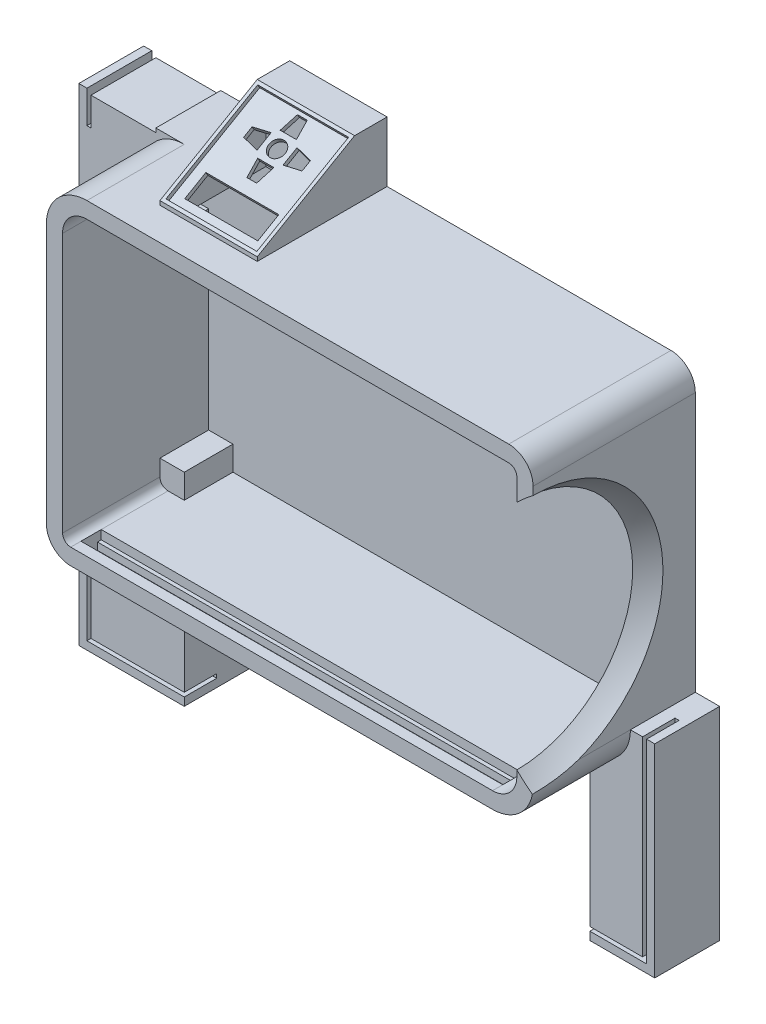
SolidWorks part; units mm, degrees
ref_plane "Front Plane" through (0, 0, 0) normal (0, 0, 1) x (1, 0, 0)
ref_plane "Top Plane" through (0, 0, 0) normal (0, 1, 0) x (1, 0, 0)
ref_plane "Right Plane" through (0, 0, 0) normal (1, 0, 0) x (0, 0, -1)
sketch "Sketch1" plane through (0, 0, 0) normal (0, 0, 1) x (1, 0, 0)
  line L1 (-190.5, -127) -> (190.5, -127)
  line L2 (-190.5, -127) -> (-190.5, 127)
  line L3 (-190.5, 127) -> (190.5, 127)
  line L4 (190.5, -127) -> (190.5, 127)
  line L5 (-190.5, -127) -> (190.5, 127) construction
  line L6 (-190.5, 127) -> (190.5, -127) construction
  point P0 (0, 0)
  dimension "D1" = 381
  dimension "D2" = 254
extrude "Boss-Extrude1" add sketch "Sketch1" against normal blind 127
fillet "Fillet5" radius 19.05 2 edges at (-190.5, -127, -63.5) (190.5, 127, -63.5)
fillet "Fillet4" radius 31.75 2 edges at (190.5, -127, -63.5) (-190.5, 127, -63.5)
sketch "Sketch3" plane through (0, 0, 0) normal (0, 0, -1) x (-1, 0, 0)
  line L16 (-158.75, -114.3) -> (171.45, -114.3)
  line L17 (-177.8, 107.95) -> (-177.8, -95.25)
  line L18 (158.75, 114.3) -> (-171.45, 114.3)
  line L19 (177.8, -107.95) -> (177.8, 95.25)
  line L20 (-158.75, -114.3) -> (171.45, -114.3)
  line L21 (-177.8, 107.95) -> (-177.8, -95.25)
  line L22 (158.75, 114.3) -> (-171.45, 114.3)
  line L23 (177.8, -107.95) -> (177.8, 95.25)
  arc A13 (-177.8, -95.25) -> (-158.75, -114.3) centre (-158.75, -95.25) ccw
  arc A14 (-171.45, 114.3) -> (-177.8, 107.95) centre (-171.45, 107.95) ccw
  arc A15 (177.8, 95.25) -> (158.75, 114.3) centre (158.75, 95.25) ccw
  arc A16 (171.45, -114.3) -> (177.8, -107.95) centre (171.45, -107.95) ccw
  arc A17 (-177.8, -95.25) -> (-158.75, -114.3) centre (-158.75, -95.25) ccw
  arc A18 (-171.45, 114.3) -> (-177.8, 107.95) centre (-171.45, 107.95) ccw
  arc A19 (177.8, 95.25) -> (158.75, 114.3) centre (158.75, 95.25) ccw
  arc A20 (171.45, -114.3) -> (177.8, -107.95) centre (171.45, -107.95) ccw
  dimension "D1" = 12.7
extrude "Cut-Extrude1" cut sketch "Sketch3" along normal offset from surface (114.3 mm away) 12.7 up to face at (0, 0, -127)
sketch "Sketch5" plane through (0, -127, 0) normal (0, -1, 0) x (1, 0, 0)
  line L0 (158.75, -127) -> (158.75, 0) construction
  line L1 (158.75, -10.455) -> (-171.45, -10.455)
  line L2 (158.75, -10.455) -> (158.75, -20.955)
  line L3 (158.75, -20.955) -> (-171.45, -20.955)
  line L4 (-171.45, -10.455) -> (-171.45, -20.955)
  line L5 (-171.45, 0) -> (-171.45, -127) construction
  line L7 (-171.45, 0) -> (158.75, 0) construction
  dimension "D1" = 10.5
  dimension "D2" = 20.955
extrude "Cut-Extrude2" cut sketch "Sketch5" against normal up to next
ref_plane "Plane1" through (0, 0, 0) normal (0, 1, 0) x (1, 0, 0)
sketch "Sketch6" plane through (0, 0, 0) normal (0, 1, 0) x (1, 0, 0)
  line L0 (139.7, 0) -> (266.7, 0)
  line L1 (171.45, 0) -> (-158.75, 0) construction
  line L2 (266.7, 0) -> (266.7, 127)
  line L3 (171.45, 127) -> (-158.75, 127) construction
  line L4 (190.5, 127) -> (190.5, 0) construction
  arc A0 (139.7, 0) -> (266.7, 127) centre (266.7, 0) cw
  dimension "D1" = 76.2
revolve "Cut-Revolve1" cut sketch "Sketch6" angle 360 about L2
sketch "Sketch7" plane through (0, 0, -127) normal (0, 0, -1) x (-1, 0, 0)
  line L0 (190.5, 95.25) -> (190.5, -107.95) construction
  line L1 (158.75, 127) -> (241.3, 127)
  line L2 (158.75, 127) -> (158.75, 50.8)
  line L3 (158.75, 50.8) -> (241.3, 50.8)
  line L4 (241.3, 127) -> (241.3, 50.8)
  line L5 (171.45, -127) -> (-158.75, -127) construction
  line L6 (234.95, 127) -> (231.775, 127)
  line L7 (234.95, 127) -> (234.95, 101.6)
  line L8 (234.95, 101.6) -> (231.775, 101.6)
  line L9 (231.775, 127) -> (231.775, 101.6)
  line L10 (-158.75, -95.25) -> (-209.55, -95.25)
  line L11 (-158.75, -95.25) -> (-158.75, -254)
  line L12 (-158.75, -254) -> (-209.55, -254)
  line L13 (-209.55, -95.25) -> (-209.55, -254)
  line L14 (0, 127) -> (0, -127) construction
  line L15 (-171.45, 127) -> (158.75, 127) construction
  line L16 (158.75, -254) -> (241.3, -254)
  line L17 (241.3, -95.25) -> (241.3, -254)
  line L18 (158.75, -95.25) -> (241.3, -95.25)
  line L19 (158.75, -95.25) -> (158.75, -254)
  line L21 (231.775, 127) -> (180.975, 127)
  line L22 (231.775, 127) -> (231.775, 123.825)
  line L23 (231.775, 123.825) -> (180.975, 123.825)
  line L24 (180.975, 127) -> (180.975, 123.825)
  line M11 (190.5, -107.95) -> (190.5, 95.25)
  arc M12 (190.5, 95.25) -> (158.75, 127) centre (158.75, 95.25) ccw
  dimension "D1" = 50.8
  dimension "D2" = 76.2
  dimension "D3" = 3.175
  dimension "D4" = 6.35
  dimension "D5" = 25.4
  dimension "D6" = 50.8
  dimension "D7" = 127
  dimension "D8" = 50.8
extrude "Boss-Extrude2" add sketch "Sketch7" against normal blind 50.8 contours L9 L1 L3 L4 L7 L8 M12 M11 | L16 L17 L18 L19 | L11 L10 L13 L12 region at (-214.1054, 88.5803, -127)
sketch "Sketch8" plane through (0, 0, -76.2) normal (0, 0, 1) x (1, 0, 0)
  line L0 (-234.95, -95.25) -> (-234.95, -247.65)
  line L1 (-190.5, -95.25) -> (-241.3, -95.25) construction
  line L2 (-234.95, -247.65) -> (-158.75, -247.65)
  line L3 (-158.75, -127) -> (-158.75, -254) construction
  line L4 (-158.75, -247.65) -> (-158.75, -244.475)
  line L5 (-158.75, -244.475) -> (-231.775, -244.475)
  line L6 (-231.775, -244.475) -> (-231.775, -95.25)
  line L7 (-231.775, -95.25) -> (-234.95, -95.25)
  line L8 (-234.95, 101.6) -> (-231.775, 101.6) construction
  line L9 (-234.95, 127) -> (-234.95, 101.6) construction
  line L10 (-158.75, -254) -> (-241.3, -254) construction
  line L11 (158.75, -247.65) -> (203.2, -247.65)
  line L12 (158.75, -127) -> (158.75, -254) construction
  line L13 (203.2, -247.65) -> (203.2, -95.25)
  line L14 (190.5, -95.25) -> (209.55, -95.25) construction
  line L15 (203.2, -95.25) -> (200.025, -95.25)
  line L16 (200.025, -95.25) -> (200.025, -244.475)
  line L17 (200.025, -244.475) -> (158.75, -244.475)
  line L18 (158.75, -244.475) -> (158.75, -247.65)
  line L19 (209.55, -95.25) -> (209.55, -254) construction
  dimension "D1" = 6.35
  dimension "D2" = 6.35
extrude "Cut-Extrude3" cut sketch "Sketch8" against normal blind 25.4
ref_plane "Plane2" through (-127, 0, 0) normal (1, 0, 0) x (0, 0, -1)
sketch "Sketch9" plane through (-127, 0, 0) normal (1, 0, 0) x (0, 0, -1)
  line L0 (25.4, 127) -> (25.4, 130.175)
  line L1 (0, 127) -> (127, 127) construction
  line L2 (25.4, 130.175) -> (101.6, 174.1691)
  line L4 (25.4, 127) -> (127, 127)
  line L5 (0, 127) -> (0, 107.95) construction
  line L6 (101.6, 174.1691) -> (127, 174.1691)
  line L7 (127, 174.1691) -> (127, 127)
  line L8 (127, 107.95) -> (127, 127) construction
  dimension "D1" = 25.4
  dimension "D3" = 25.4
  dimension "D4" = 3.175
  dimension "D5" = 60
extrude "Boss-Extrude3" add sketch "Sketch9" along normal blind 76.2
sketch "Sketch10" plane through (0, 86.6327, 50.0174) normal (0, 0.866, 0.5) x (1, 0, 0)
  line L8 (-124.46, 172.5327) -> (-124.46, 89.6245)
  line L9 (-124.46, 89.6245) -> (-53.34, 89.6245)
  line L10 (-53.34, 89.6245) -> (-53.34, 172.5327)
  line L11 (-53.34, 172.5327) -> (-124.46, 172.5327)
  line L12 (-124.46, 172.5327) -> (-124.46, 89.6245)
  line L13 (-124.46, 89.6245) -> (-53.34, 89.6245)
  line L14 (-53.34, 89.6245) -> (-53.34, 172.5327)
  line L15 (-53.34, 172.5327) -> (-124.46, 172.5327)
  dimension "D1" = 2.54
extrude "Cut-Extrude4" cut sketch "Sketch10" against normal blind 12.7
sketch "Sketch11" plane through (0, 114.3, 0) normal (0, -1, 0) x (1, 0, 0)
  line L0 (-124.46, -33.9497) -> (-53.34, -33.9497) construction
  line L1 (-124.46, -33.9497) -> (-53.34, -33.9497)
  line L2 (-124.46, -33.9497) -> (-124.46, -105.7503)
  line L3 (-124.46, -105.7503) -> (-53.34, -105.7503)
  line L4 (-53.34, -33.9497) -> (-53.34, -105.7503)
  line L5 (-124.46, -105.7503) -> (-124.46, -33.9497) construction
  line L6 (-53.34, -105.7503) -> (-124.46, -105.7503) construction
  line L7 (-53.34, -33.9497) -> (-53.34, -105.7503) construction
extrude "Cut-Extrude5" cut sketch "Sketch11" against normal up to surface (6.1465 mm away) up to face at (-88.9, 141.1735, -69.85)
ref_plane "Plane3" through (0, 83.8831, 48.4299) normal (0, 0.866, 0.5) x (1, 0, 0)
sketch "Sketch12" plane through (0, 83.8831, 48.4299) normal (0, 0.866, 0.5) x (1, 0, 0)
  line L0 (-53.34, 89.6245) -> (-53.34, 172.5327) construction
  line L1 (-124.46, 89.6245) -> (-53.34, 89.6245) construction
  line L2 (-124.46, 172.5327) -> (-124.46, 89.6245) construction
  line L3 (-53.34, 172.5327) -> (-124.46, 172.5327) construction
  line L4 (-53.34, 89.6245) -> (-53.34, 172.5327)
  line L5 (-124.46, 89.6245) -> (-53.34, 89.6245)
  line L6 (-124.46, 172.5327) -> (-124.46, 89.6245)
  line L7 (-53.34, 172.5327) -> (-124.46, 172.5327)
  line L8 (-88.9, 172.5327) -> (-88.9, 89.6245) construction
  line L9 (-82.55, 136.9727) -> (-95.25, 136.9727)
  line L10 (-78.74, 153.4827) -> (-66.04, 150.9427)
  line L11 (-78.74, 153.4827) -> (-78.74, 140.7827)
  line L12 (-78.74, 140.7827) -> (-66.04, 143.3227)
  line L13 (-66.04, 150.9427) -> (-66.04, 143.3227)
  line L14 (-82.55, 136.9727) -> (-85.09, 124.2727)
  line L15 (-85.09, 124.2727) -> (-92.71, 124.2727)
  line L16 (-95.25, 136.9727) -> (-92.71, 124.2727)
  line L17 (-99.06, 140.7827) -> (-99.06, 153.4827)
  line L18 (-99.06, 140.7827) -> (-111.76, 143.3227)
  line L19 (-111.76, 143.3227) -> (-111.76, 150.9427)
  line L20 (-99.06, 153.4827) -> (-111.76, 150.9427)
  line L21 (-95.25, 157.2927) -> (-82.55, 157.2927)
  line L22 (-95.25, 157.2927) -> (-92.71, 169.9927)
  line L23 (-92.71, 169.9927) -> (-85.09, 169.9927)
  line L24 (-82.55, 157.2927) -> (-85.09, 169.9927)
  line L26 (-116.84, 95.9745) -> (-59.69, 95.9745)
  line L27 (-116.84, 95.9745) -> (-116.84, 115.0245)
  line L28 (-116.84, 115.0245) -> (-59.69, 115.0245)
  line L29 (-59.69, 95.9745) -> (-59.69, 115.0245)
  circle A0 centre (-88.9, 147.1327) radius 6.35
  point P20 (-88.9, 153.4827)
  dimension "D1" = 12.7
  dimension "D2" = 12.7
  dimension "D3" = 10.16
  dimension "D4" = 7.62
  dimension "D5" = 12.7
  dimension "D6" = 25.4
  dimension "D8" = 57.15
  dimension "D9" = 19.05
  dimension "D10" = 6.35
  dimension "D11" = 6.35
  dimension "D7" = 4
extrude "Boss-Extrude4" add sketch "Sketch12" against normal blind 3.175
sketch "Sketch13" plane through (0, -114.3, 0) normal (0, 1, 0) x (1, 0, 0)
  line L8 (-6.35, 20.955) -> (-6.35, 10.455) construction
  line L10 (-171.45, 20.955) -> (158.75, 20.955) construction
  line L12 (158.75, 10.455) -> (-171.45, 10.455) construction
  line L13 (-171.45, 15.955) -> (158.75, 15.955) construction
  line L16 (158.75, 76.2) -> (158.75, 20.955) construction
  line L17 (-171.45, 8.0175) -> (158.75, 8.0175)
  line L18 (-171.45, 8.0175) -> (-171.45, 23.8925)
  line L19 (-171.45, 23.8925) -> (158.75, 23.8925)
  line L20 (158.75, 8.0175) -> (158.75, 23.8925)
  line L21 (-171.45, 15.705) -> (158.75, 15.705) construction
  line L22 (-171.45, 10.455) -> (-171.45, 20.955) construction
  line L23 (158.75, 20.955) -> (158.75, 10.455) construction
  dimension "D1" = 15.875
  dimension "D2" = 0.25
extrude "Cut-Extrude6" cut sketch "Sketch13" against normal blind 7
sketch "Sketch14" plane through (-234.95, 0, 0) normal (1, 0, 0) x (0, 0, -1)
  line L0 (76.2, 127) -> (76.2, 101.6) construction
  line L5 (76.2, 127) -> (127, 127) construction
  line L8 (80.2, 54.8) -> (114.3, 54.8)
  line L9 (80.2, 54.8) -> (80.2, 121)
  line L10 (80.2, 121) -> (114.3, 121)
  line L11 (114.3, 54.8) -> (114.3, 121)
  line L12 (76.2, 50.8) -> (127, 50.8) construction
  line L14 (114.3, -95.25) -> (114.3, 95.25) construction
  point P0 (97.25, 88.9)
  dimension "D1" = 6
  dimension "D2" = 4
  dimension "D3" = 4
extrude "Cut-Extrude7" cut sketch "Sketch14" along normal up to surface (57.15 mm away) up to face at (-177.8, -35.9833, -63.5)
sketch "Sketch15" plane through (0, 0, -114.3) normal (0, 0, 1) x (1, 0, 0)
  line L6 (-158.75, 114.3) -> (-177.8, 114.3)
  line L7 (-177.8, 95.25) -> (-177.8, 121) construction
  line L8 (-177.8, 114.3) -> (-177.8, 95.25)
  arc A0 (-158.75, 114.3) -> (-177.8, 95.25) centre (-158.75, 95.25) ccw construction
  arc A1 (-158.75, 114.3) -> (-177.8, 95.25) centre (-158.75, 95.25) ccw
extrude "Cut-Extrude8" cut sketch "Sketch15" along normal up to surface (34.1 mm away) up to face at (-209.55, 92.8643, -80.2)
sketch "Sketch16" plane through (0, 0, -114.3) normal (0, 0, 1) x (1, 0, 0)
  line L0 (-231.775, 121) -> (-231.775, 101.6) construction
  line L1 (-231.775, 118) -> (-220.775, 118)
  line L2 (-231.775, 118) -> (-231.775, 98)
  line L3 (-231.775, 98) -> (-220.775, 98)
  line L4 (-220.775, 118) -> (-220.775, 98)
  line L5 (-177.8, 121) -> (-231.775, 121) construction
  dimension "D1" = 11
  dimension "D2" = 20
  dimension "D3" = 3
extrude "Boss-Extrude5" add sketch "Sketch16" along normal blind 5
sketch "Sketch17" plane through (0, 0, -109.3) normal (0, 0, 1) x (1, 0, 0)
  line L0 (-231.775, 98) -> (-220.775, 98) construction
  line L1 (-220.775, 98) -> (-220.775, 118) construction
  circle A0 centre (-223.675, 112.5) radius 2
  circle A1 centre (-223.675, 103) radius 2
  point P8 (0, 0)
  dimension "D4" = 4
  dimension "D1" = 9.5
  dimension "D2" = 14.5
  dimension "D3" = 2.9
extrude "Cut-Extrude9" cut sketch "Sketch17" against normal through all
